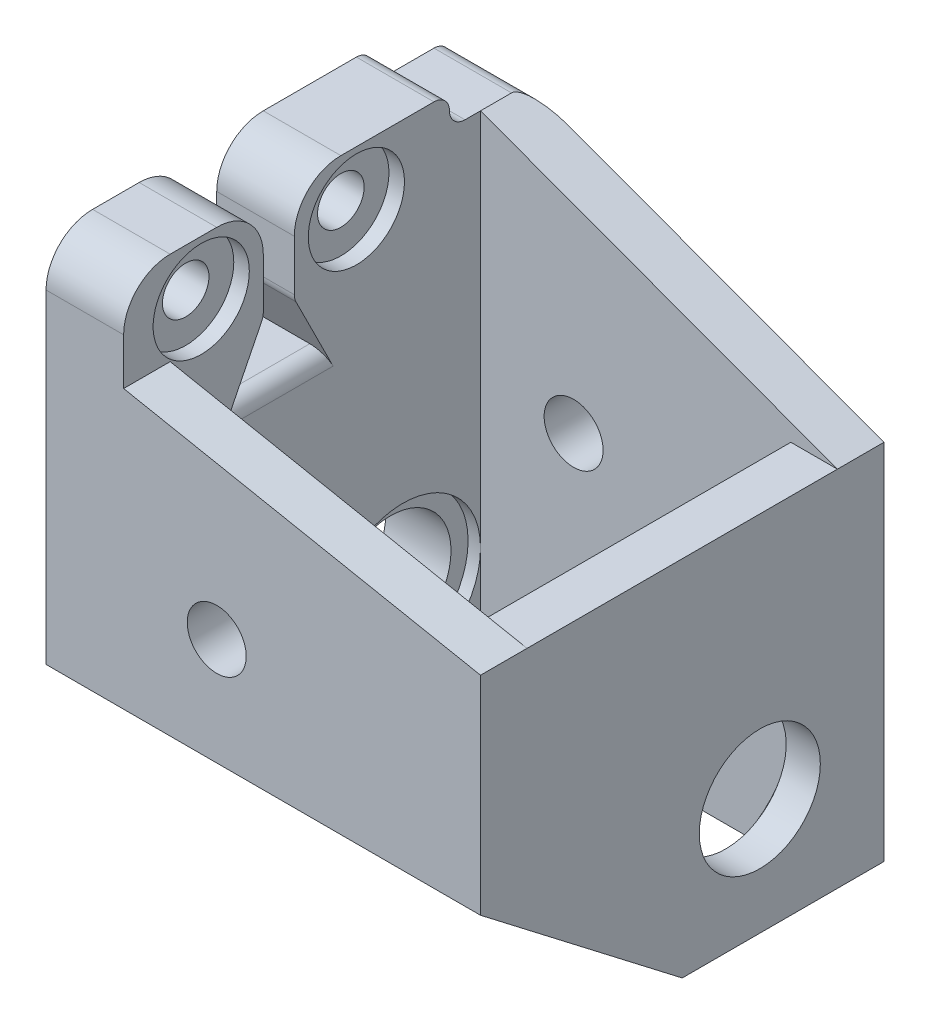
SolidWorks part; units mm, degrees
other "标注1"
sketch "草图49" plane through (13, 10.3992, -3) normal (0.763, 0.5413, -0.3534) x (-0.4894, 0.1265, -0.8629)
material "ABS"
ref_plane "前视基准面" through (0, 0, 0) normal (0, 0, 1) x (1, 0, 0)
ref_plane "上视基准面" through (0, 0, 0) normal (0, 1, 0) x (1, 0, 0)
ref_plane "右视基准面" through (0, 0, 0) normal (1, 0, 0) x (0, 0, -1)
sketch "草图1" plane through (0, 0, 0) normal (0, 0, 1) x (1, 0, 0)
  line L0 (10, 0) -> (-10, 0)
  line L1 (0, 4.2473) -> (0, -34.6143) construction
  line L2 (-10, 0) -> (-10, -57.766)
  line L3 (-10, -57.766) -> (10, -57.766)
  line L4 (10, 0) -> (10, -57.766)
  point P8 (0, -57.766)
  point P9 (0, 0)
extrude "凸台-拉伸1" add sketch "草图1" against normal blind 3
sketch "草图2" plane through (-10, 0, 0) normal (-1, 0, 0) x (0, 0, 1)
  line L1 (-3, 0) -> (23, 0)
  line L2 (-3, 0) -> (-3, -57.766)
  line L3 (-3, -57.766) -> (23, -57.766)
  line L4 (23, 0) -> (23, -57.766)
extrude "凸台-拉伸2" add sketch "草图2" along normal blind 3
sketch "草图3" plane through (0, 0, 0) normal (0, 0, 1) x (1, 0, 0)
  line L0 (-10, -5.5) -> (10, -5.5)
  line L1 (-10, -57.766) -> (-10, 0) construction
  line L2 (10, -57.766) -> (10, 0) construction
  line L3 (10, 0) -> (-10, 0) construction
  dimension "D1" = 5.5
sketch "草图4" plane through (-10, 0, 0) normal (1, 0, 0) x (0, 0, -1)
  line L0 (-23, -5.5) -> (0, -5.5)
  line L1 (-23, -57.766) -> (-23, 0) construction
  line L2 (0, 0) -> (0, -57.766) construction
  line L3 (-23, 0) -> (0, 0) construction
  dimension "D1" = 5.5
sketch "草图7" plane through (-10, 0, 0) normal (1, 0, 0) x (0, 0, -1)
  line L0 (-23, -14.9) -> (0, -14.9)
  line L1 (-23, -57.766) -> (-23, 0) construction
  line L2 (0, -57.766) -> (0, 0) construction
  line L3 (-23, -5.5) -> (0, -5.5) construction
  circle A0 centre (-5, -14.9) radius 3.9
  point P8 (-5, -14.9)
  dimension "D1" = 9.4
  dimension "D2" = 5
extrude "切除-拉伸1" cut sketch "草图7" against normal blind 6 contours L0 A0 | L0 A0 region at (-10, -13.2448, 5) region at (-10, -16.5552, 5)
sketch "草图8" plane through (-13, 0, 0) normal (-1, 0, 0) x (0, 0, 1)
  circle A0 centre (5, -14.9) radius 4.48
extrude "切除-拉伸2" cut sketch "草图8" against normal blind 0.8
sketch "草图9" plane through (0, 0, 0) normal (0, 0, 1) x (1, 0, 0)
  line L0 (-10, -5.5) -> (10, -5.5) construction
  circle A0 centre (-4, -5.5) radius 1.9
  point P0 (-4, -5.5)
  point P1 (-10, -5.5)
  point P4 (-4, -5.5)
  dimension "D1" = 6
extrude "切除-拉伸3" cut sketch "草图9" against normal blind 3.8
sketch "草图10" plane through (0, 0, 0) normal (0, 0, 1) x (1, 0, 0)
  line L0 (0, 1.0359) -> (0, 0) construction
  line L1 (0, 0) -> (0, -59.324) construction
ref_plane "基准面1" through (0, 0, 0) normal (1, 0, 0) x (0, 0, -1)
mirror "镜向1" about plane through (0, 0, 0) normal (1, 0, 0) of "凸台-拉伸2"
mirror "镜向2" about plane through (0, 0, 0) normal (1, 0, 0) of "切除-拉伸1", "切除-拉伸2"
ref_plane "基准面2" through (0, 0, 10) normal (0, 0, 1) x (1, 0, 0)
mirror "镜向3" about plane through (0, 0, 10) normal (0, 0, 1) of "凸台-拉伸1"
mirror "镜向5" about plane through (0, 0, 10) normal (0, 0, 1) of "切除-拉伸3"
sketch "草图12" plane through (13, 0, 0) normal (1, 0, 0) x (0, 0, -1)
  line L0 (-23, -22.4) -> (3, -22.4)
  line L1 (-23, -57.766) -> (-23, 0) construction
  line L2 (3, 0) -> (3, -57.766) construction
  line L5 (-23, -22.4) -> (-23, -57.766)
  line L6 (-23, -57.766) -> (3, -57.766)
  line L7 (3, -22.4) -> (3, -57.766)
  circle A0 centre (-5, -14.9) radius 3.9 construction
  dimension "D1" = 7.5
extrude "切除-拉伸4" cut sketch "草图12" against normal blind 36
sketch "草图22" plane through (13, 0, 0) normal (1, 0, 0) x (0, 0, -1)
  line L0 (-23, -12.4) -> (-23, -22.4)
  line L1 (-23, -22.4) -> (-23, 0) construction
  line L2 (-23, -22.4) -> (-10, -22.4)
  line L3 (3, -22.4) -> (-23, -22.4) construction
  line L4 (-23, -12.4) -> (-10, -22.4)
extrude "切除-拉伸8" cut sketch "草图22" against normal blind 28
sketch "草图23" plane through (0, 0, 0) normal (0, 1, 0) x (1, 0, 0)
  line L1 (-10, 0) -> (10, 0)
  line L2 (-10, 0) -> (-10, -20)
  line L3 (-10, -20) -> (10, -20)
  line L4 (10, 0) -> (10, -20)
  line L5 (13, -23) -> (-13, -23)
  line L6 (13, -23) -> (13, 3)
  line L7 (13, 3) -> (-13, 3)
  line L8 (-13, -23) -> (-13, 3)
extrude "凸台-拉伸7" add sketch "草图23" along normal blind 4
sketch "草图24" plane through (0, 4, 0) normal (0, 1, 0) x (1, 0, 0)
  line L0 (10, -20) -> (10, 0) construction
  line L1 (-10, 0) -> (10, 0)
  line L2 (-10, 0) -> (-10, -20)
  line L3 (-10, -20) -> (10, -20)
  line L4 (10, 0) -> (10, -20)
extrude "凸台-拉伸8" add sketch "草图24" against normal blind 3
sketch "草图25" plane through (0, 4, 0) normal (0, 1, 0) x (1, 0, 0)
  line L0 (13, -23) -> (13, 3) construction
  line L4 (13, -23) -> (18, -23)
  line L5 (13, -23) -> (13, -7)
  line L6 (13, -7) -> (18, -7)
  line L7 (18, -23) -> (18, -7)
  circle A0 centre (15.5, -20.2333) radius 1.5
  circle A1 centre (15.5, -10.2333) radius 1.5
  point P0 (13, -15)
  dimension "D1" = 8
extrude "凸台-拉伸9" add sketch "草图25" against normal blind 3 contours A1 | A0 | L5 L4 L7 L6 region at (15.5, 4, 20.2333) region at (15.5, 4, 10.2333)
fillet "圆角1" radius 1 1 edges at (18, 1, 15)
sketch "草图26" plane through (13, 0, 0) normal (1, 0, 0) x (0, 0, -1)
  line L0 (-23, 1) -> (-7, 1) construction
  line L1 (-16, 1) -> (-14, 1)
  arc A0 (-16, 1) -> (-14, 1) centre (-15, 1) ccw
extrude "切除-拉伸9" cut sketch "草图26" against normal blind 3
sketch "草图27" plane through (0, 4, 0) normal (0, 1, 0) x (1, 0, 0)
  circle A0 centre (7.5, -15.2333) radius 1.5
extrude "切除-拉伸10" cut sketch "草图27" against normal blind 3
sketch "草图28" plane through (0, 1, 0) normal (0, -1, 0) x (1, 0, 0)
  line L1 (-10, 20) -> (10, 20)
  line L2 (-10, 20) -> (-10, 0)
  line L3 (-10, 0) -> (10, 0)
  line L4 (10, 20) -> (10, 0)
extrude "切除-拉伸11" cut sketch "草图28" against normal blind 10
sketch "草图29" plane through (0, 0, -3) normal (0, 0, -1) x (-1, 0, 0)
  line L1 (13, 4) -> (-24.6816, 4)
  line L2 (13, 4) -> (13, 1)
  line L3 (13, 1) -> (-24.6816, 1)
  line L4 (-24.6816, 4) -> (-24.6816, 1)
extrude "切除-拉伸12" cut sketch "草图29" against normal blind 42
sketch "草图31" plane through (-12.2, 0, 0) normal (-1, 0, 0) x (0, 0, 1)
  circle A0 centre (5, -14.9) radius 3.98
  circle A1 centre (5, -14.9) radius 4.48
extrude "凸台-拉伸13" add sketch "草图31" along normal blind 0.8
sketch "草图32" plane through (-10, 0, 0) normal (1, 0, 0) x (0, 0, -1)
  circle A0 centre (-5, -14.9) radius 3.98
  circle A1 centre (-5, -14.9) radius 5
extrude "切除-拉伸13" cut sketch "草图32" against normal blind 0.8
sketch "草图33" plane through (13, 0, 0) normal (1, 0, 0) x (0, 0, -1)
  circle A0 centre (-5, -14.9) radius 4.48
extrude "凸台-拉伸14" add sketch "草图33" against normal blind 3
mirror "镜向6" about plane through (0, 0, 0) normal (1, 0, 0) of "切除-拉伸1", "切除-拉伸13"
sketch "草图36" plane through (-10.8, 0, 0) normal (1, 0, 0) x (0, 0, -1)
  circle A0 centre (-5, -14.9) radius 5
extrude "切除-拉伸14" cut sketch "草图36" along normal blind 3
mirror "镜向7" about plane through (0, 0, 0) normal (1, 0, 0) of "切除-拉伸14"
sketch "草图37" plane through (-12.2, 0, 0) normal (-1, 0, 0) x (0, 0, 1)
  circle A0 centre (5, -14.9) radius 3.9
  circle A1 centre (5, -14.9) radius 3.98
extrude "凸台-拉伸17" add sketch "草图37" along normal up to surface (0.8 mm away) up to face at (-13, -11.04, 10)
sketch "草图38" plane through (-13, 0, 0) normal (-1, 0, 0) x (0, 0, 1)
  line L0 (13, 1) -> (13, 8)
  line L1 (23, 1) -> (-3, 1) construction
  line L3 (11, 10.3992) -> (5, 10.3992)
  line L4 (15, 1) -> (21, 1)
  line L5 (15, 1) -> (15, 10.3992)
  line L6 (15, 10.3992) -> (21, 10.3992)
  line L7 (21, 1) -> (21, 10.3992)
  line L8 (5, 1) -> (5, 10.3992)
  line L9 (11, 1) -> (5, 1)
  line L10 (11, 1) -> (11, 10.3992)
  circle A0 centre (18, 8) radius 1.5
  circle A2 centre (8, 8) radius 1.5
  line M9 (23, 1) -> (-3, 1)
  dimension "D1" = 2
  dimension "D2" = 3
  dimension "D3" = 6
extrude "凸台-拉伸18" add sketch "草图38" against normal blind 3 contours L7 L6 L5 A0 M9 | L10 L3 L8 A2 M9 region at (-13, 5.37, 8) region at (-13, 5.37, 18)
sketch "草图39" plane through (13, 0, 0) normal (1, 0, 0) x (0, 0, -1)
  line L0 (-23, 1) -> (-16, 1) construction
  line L1 (-17.3818, 1) -> (-13.1942, 1)
  line L2 (-17.3818, 1) -> (-17.3818, -0.3609)
  line L3 (-17.3818, -0.3609) -> (-13.1942, -0.3609)
  line L4 (-13.1942, 1) -> (-13.1942, -0.3609)
extrude "凸台-拉伸19" add sketch "草图39" against normal blind 3
sketch "草图43" plane through (-13, 0, 0) normal (-1, 0, 0) x (0, 0, 1)
  line L0 (-3, 1) -> (5, 1)
  line L1 (5, 1) -> (5, 10.3992)
  line L2 (5, 10.3992) -> (11, 10.3992)
  line L3 (11, 10.3992) -> (11, 1)
  line L4 (11, 1) -> (15, 1)
  line L5 (15, 1) -> (15, 10.3992)
  line L6 (15, 10.3992) -> (21, 10.3992)
  line L7 (21, 10.3992) -> (21, 1)
  line L8 (21, 1) -> (23, 1)
  line L9 (23, 1) -> (23, -12.4)
  line L10 (23, -12.4) -> (10, -22.4)
  line L11 (10, -22.4) -> (-3, -22.4)
  line L12 (-3, -22.4) -> (-3, 1)
  circle A0 centre (8, 8) radius 1.5
  circle A1 centre (18, 8) radius 1.5
  circle A2 centre (5, -14.9) radius 3.9
extrude "凸台-拉伸22" add sketch "草图43" along normal blind 2
sketch "草图44" plane through (0, 0, 21) normal (0, 0, 1) x (1, 0, 0)
  line L1 (-15, 10.3992) -> (-10, 10.3992)
  line L2 (-15, 10.3992) -> (-15, 1)
  line L3 (-15, 1) -> (-10, 1)
  line L4 (-10, 10.3992) -> (-10, 1)
extrude "凸台-拉伸23" add sketch "草图44" along normal up to surface (2 mm away) up to face at (-4, -3.6, 23)
sketch "草图45" plane through (0, 0, 23) normal (0, 0, 1) x (1, 0, 0)
  line L1 (-10, 1) -> (13, 1)
  line L3 (-10, 1) -> (-10, 5.5)
  line L7 (-10, 10.3992) -> (-10, 1) construction
  line L8 (-10, 5.5) -> (13, 1)
extrude "凸台-拉伸24" add sketch "草图45" against normal up to surface (3 mm away) up to face at (0, -6.8538, 20)
sketch "草图47" plane through (0, 0, 5) normal (0, 0, -1) x (-1, 0, 0)
  line L6 (10, 1) -> (15, 1)
  line L7 (10, 1) -> (10, 10.3992)
  line L8 (10, 10.3992) -> (15, 10.3992)
  line L9 (15, 1) -> (15, 10.3992)
extrude "凸台-拉伸25" add sketch "草图47" along normal up to surface (8 mm away) up to face at (-2.1, -5.5, -3)
sketch "草图51" plane through (0, 10.3992, 0) normal (0, 1, 0) x (1, 0, 0)
  line L1 (-15, 3) -> (-10, 3)
  line L2 (-15, 3) -> (-15, -11)
  line L3 (-15, -11) -> (-10, -11)
  line L4 (-10, 3) -> (-10, -11)
  line L5 (-15, -15) -> (-10, -15)
  line L6 (-15, -15) -> (-15, -23)
  line L7 (-15, -23) -> (-10, -23)
  line L8 (-10, -15) -> (-10, -23)
extrude "凸台-拉伸28" add sketch "草图51" along normal blind 1.1
sketch "草图53" plane through (-10, 0, 0) normal (1, 0, 0) x (0, 0, -1)
  line L1 (3, 11.4992) -> (-2, 11.4992)
  line L2 (3, 11.4992) -> (3, 9.4992)
  line L3 (3, 9.4992) -> (-2, 9.4992)
  line L4 (-2, 11.4992) -> (-2, 9.4992)
extrude "切除-拉伸16" cut sketch "草图53" against normal blind 6.1
fillet "圆角9" radius 1 2 edges at (-12.5, 9.4992, 2) (-12.5, 11.4992, 2)
sketch "草图54" plane through (0, 0, -3) normal (0, 0, -1) x (-1, 0, 0)
  line L0 (-13, 1) -> (10, 1)
  line L1 (10, 1) -> (10, 9.4992)
  line L2 (10, 9.4992) -> (-13, 1)
extrude "凸台-拉伸30" add sketch "草图54" against normal up to surface (3 mm away) up to face at (0, -12.1, 0)
fillet "圆角10" radius 1 1 edges at (-12.5, 9.4992, -3)
sketch "草图56" plane through (-10, 0, 0) normal (1, 0, 0) x (0, 0, -1)
  circle A0 centre (-18, 8) radius 3
  circle A1 centre (-8, 8) radius 3
sketch "草图57" plane through (0, 0, 15) normal (0, 0, -1) x (-1, 0, 0)
  line L6 (15, 1) -> (10, 1)
  line L7 (15, 1) -> (15, 11.4992)
  line L8 (15, 11.4992) -> (10, 11.4992)
  line L9 (10, 1) -> (10, 11.4992)
extrude "凸台-拉伸31" add sketch "草图57" along normal blind 1
sketch "草图58" plane through (0, 0, 11) normal (0, 0, 1) x (1, 0, 0)
  line L1 (-15, 11.4992) -> (-10, 11.4992)
  line L2 (-15, 11.4992) -> (-15, 1)
  line L3 (-15, 1) -> (-10, 1)
  line L4 (-10, 11.4992) -> (-10, 1)
extrude "凸台-拉伸32" add sketch "草图58" along normal blind 1
sketch "草图59" plane through (-10, 0, 0) normal (1, 0, 0) x (0, 0, -1)
  circle A0 centre (-18, 8) radius 3.1
  circle A1 centre (-8, 8) radius 3.1
fillet "圆角11" radius 3 3 edges at (-12.5, 11.4992, 12) (-12.5, 11.4992, 14) (-12.5, 11.4992, 23)
sketch "草图61" plane through (-10, 0, 0) normal (1, 0, 0) x (0, 0, -1)
  line L0 (-12, 1) -> (-12, 5)
  line L1 (-12, 1) -> (-12, 8.4992) construction
  line L2 (-12, 5) -> (-10, 1)
  line L3 (-10, 1) -> (-12, 1)
  line L4 (-14, 1) -> (-14, 5)
  line L5 (-14, 8.4992) -> (-14, 1) construction
  line L6 (-14, 5) -> (-16, 1)
  line L7 (-16, 1) -> (-14, 1)
extrude "切除-拉伸19" cut sketch "草图61" against normal blind 6.5
fillet "圆角14" radius 1 1 edges at (-10, 1, 13)
fillet "圆角19" radius 1 2 edges at (-12.5, 5, 12) (-12.5, 5, 14)
sketch "草图62" plane through (-10, 0, 0) normal (1, 0, 0) x (0, 0, -1)
  circle A0 centre (-18, 8) radius 3.1
  circle A1 centre (-8, 8) radius 3.1
extrude "切除-拉伸20" cut sketch "草图62" against normal blind 1
